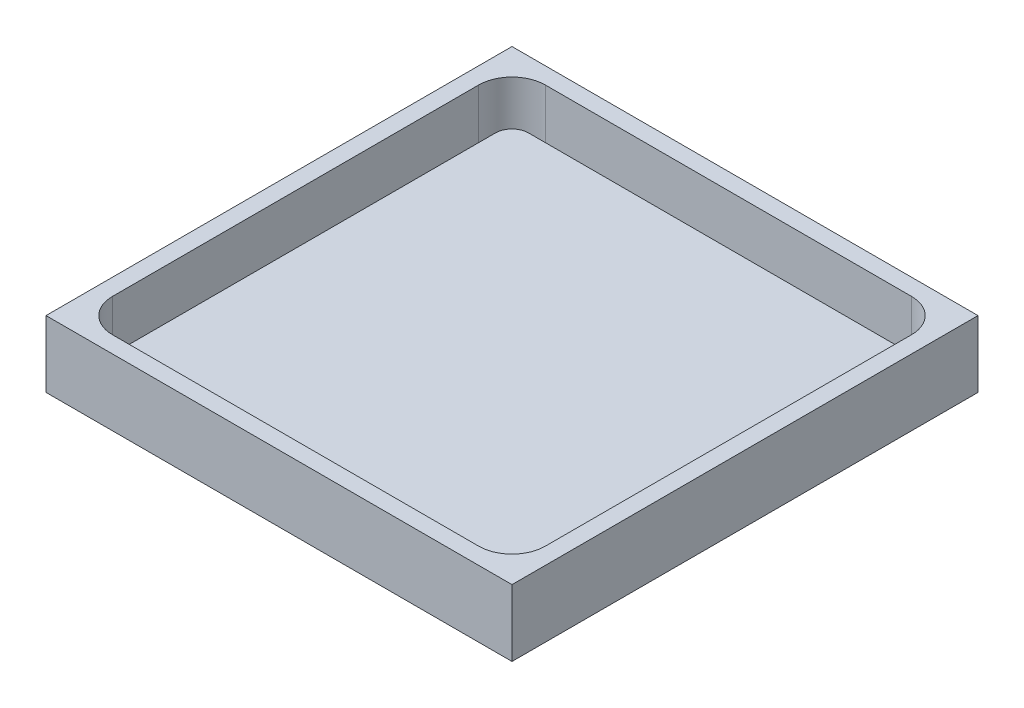
SolidWorks part; units mm, degrees
ref_plane "Front Plane" through (0, 0, 0) normal (0, 0, 1) x (1, 0, 0)
ref_plane "Top Plane" through (0, 0, 0) normal (0, 1, 0) x (1, 0, 0)
ref_plane "Right Plane" through (0, 0, 0) normal (1, 0, 0) x (0, 0, -1)
sketch "Sketch1" plane through (0, 0, 0) normal (0, 1, 0) x (1, 0, 0)
  line L1 (-12, -12) -> (12, -12)
  line L2 (-12, -12) -> (-12, 12)
  line L3 (-12, 12) -> (12, 12)
  line L4 (12, -12) -> (12, 12)
  line L5 (-12, -12) -> (12, 12) construction
  line L6 (-12, 12) -> (12, -12) construction
  line L7 (-13, -13) -> (13, -13)
  line L8 (-13, -13) -> (-13, 13)
  line L9 (-13, 13) -> (13, 13)
  line L10 (13, -13) -> (13, 13)
  line L11 (-13, -13) -> (13, 13) construction
  line L12 (-13, 13) -> (13, -13) construction
  line L13 (-14, -14) -> (14, -14)
  line L14 (-14, -14) -> (-14, 14)
  line L15 (-14, 14) -> (14, 14)
  line L16 (14, -14) -> (14, 14)
  line L17 (-14, -14) -> (14, 14) construction
  line L18 (-14, 14) -> (14, -14) construction
  point P0 (0, 0)
  point P6 (0, 0)
  point P11 (0, 0)
  dimension "D1" = 24
  dimension "D2" = 24
  dimension "D3" = 26
  dimension "D4" = 26
  dimension "D5" = 28
  dimension "D6" = 28
extrude "Boss-Extrude1" add sketch "Sketch1" along normal blind 1 contours L7 L10 L9 L8 L4 L1 L2 L3 region at (-12.6323, 0, 0)
extrude "Boss-Extrude2" add sketch "Sketch1<3>" along normal blind 2 contours L1 L4 L3 L2 region at (0, 0, 0)
sketch "Sketch1<3>" plane through (0, 0, 0) normal (0, 1, 0) x (1, 0, 0) same geometry as "Sketch1"
extrude "Boss-Extrude3" add sketch "Sketch1<4>" along normal blind 4 contours L13 L16 L15 L14 L10 L7 L8 L9 region at (-13.604, 0, 0)
sketch "Sketch1<4>" plane through (0, 0, 0) normal (0, 1, 0) x (1, 0, 0) same geometry as "Sketch1"
fillet "Fillet1" radius 1 4 edges at (12, 1.5, -12) (12, 1.5, 12) (-12, 1.5, -12) (-12, 1.5, 12)
fillet "Fillet2" radius 2 4 edges at (-13, 2.5, -13) (13, 2.5, -13) (13, 2.5, 13) (-13, 2.5, 13)
